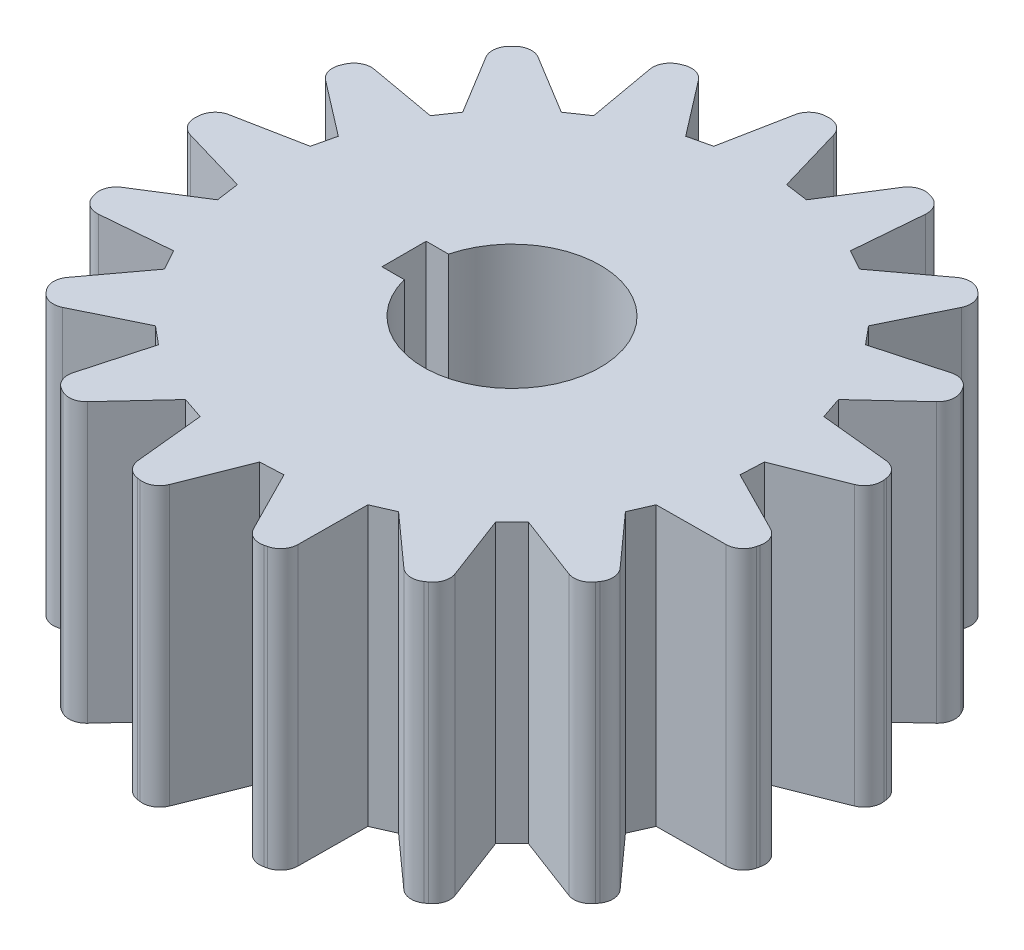
SolidWorks part; units mm, degrees
note: '?' marks a value the reader was unsure of.
ref_plane "Plan de face" through (0, 0, 0) normal (0, 0, 1) x (1, 0, 0)
ref_plane "Plan de dessus" through (0, 0, 0) normal (0, 1, 0) x (1, 0, 0)
ref_plane "Plan de droite" through (0, 0, 0) normal (1, 0, 0) x (0, 0, -1)
sketch "Esquisse1" plane through (0, 0, 0) normal (0, 0, 1) x (1, 0, 0)
  line L0 (-47.5, 40) -> (-47.5, 0)
  line L1 (-40, 40) -> (0, 40)
  line L2 (0, 40) -> (0, 0)
  line L3 (0, 40) -> (0, 0) construction
  line L4 (0, 0) -> (-40, 0)
  line L18 (-47.5, 40) -> (-40, 40)
  line L19 (-40, 40) -> (-40, 0) construction
  line L20 (-40, 0) -> (-47.5, 0)
  dimension "D2" = 40
  dimension "D3" = 47.5
  dimension "D15" = 40
revolve "Révolution1" add sketch "Esquisse1" angle 360 about L3
sketch "Esquisse5" plane through (0, 40, 0) normal (0, 1, 0) x (1, 0, 0)
  line L0 (0, 0) -> (0, 47.5) construction
  line L1 (0, 0) -> (-17.159, 44.2924) construction
  line L2 (-17.159, 44.2924) -> (-9.9203, 34.8662)
  line L3 (-9.9203, 34.8662) -> (-6.6609, 35.6328)
  line L4 (-6.6609, 35.6328) -> (-4.3827, 47.2974)
  line L5 (-4.3827, 47.2974) -> (0, 47.5)
  line L6 (-4.3827, 47.2974) -> (0, 0) construction
  line L7 (-6.6609, 35.6328) -> (0, 0) construction
  line L8 (-9.9203, 34.8662) -> (0, 0) construction
  line L9 (0, 47.5) -> (0, 108.0563)
  line L10 (0, 108.0563) -> (-38.2804, 98.3017)
  line L11 (-38.2804, 98.3017) -> (-17.159, 44.2924)
  circle A0 centre (0, 0) radius 47.5 construction
  circle A1 centre (0, 0) radius 36.25 construction
  circle A2 centre (0, 0) radius 47.5 construction
  dimension "D1" = 21.176
  dimension "D2" = 5.294
  dimension "D3" = 5.294
  dimension "D5" = 72.5
  dimension "D4" = 5.294
extrude "Enlèv. mat.-Extru.3" cut sketch "Esquisse5" against normal through all
fillet "Congé1" radius 2.5 2 edges at (-17.159, 20, -44.2924) (-4.3827, 20, -47.2974)
ref_axis "Axe1" through (0, 39.3, 0) along (0, -1, 0)?
pattern_circular "Répétition circulaire1" count 17 over 360 about axis through (0, 0, 0) along (0, 1, 0) of "Enlèv. mat.-Extru.3", "Congé1"
sketch "Esquisse6" plane through (0, 40, 0) normal (0, 1, 0) x (1, 0, 0)
  line L0 (0, 0) -> (-12.7, 0) construction
  line L1 (-12.2967, 3.175) -> (-15.4967, 3.175)
  line L2 (-15.4967, 3.175) -> (-15.4967, -3.175)
  line L3 (-15.4967, -3.175) -> (-12.2967, -3.175)
  line L4 (-12.7, 0) -> (-15.4967, 0) construction
  circle A0 centre (0, 0) radius 12.7 construction
  arc A1 (-12.2967, 3.175) -> (-12.2967, -3.175) centre (0, 0) cw
  dimension "D3" = 25.4
  dimension "D1" = 6.35
  dimension "D2" = 3.2
extrude "Enlèv. mat.-Extru.4" cut sketch "Esquisse6" against normal through all
